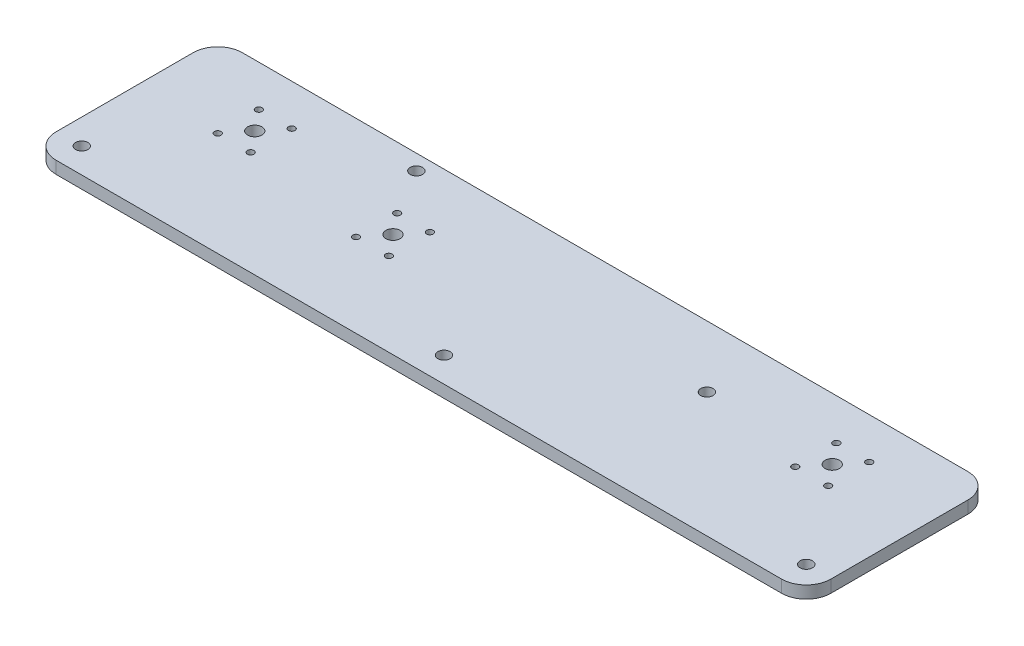
SolidWorks part; units mm, degrees
material "Policarbonato"
ref_plane "Plano frontal" through (0, 0, 0) normal (0, 0, 1) x (1, 0, 0)
ref_plane "Plano superior" through (0, 0, 0) normal (0, 1, 0) x (1, 0, 0)
ref_plane "Plano direito" through (0, 0, 0) normal (1, 0, 0) x (0, 0, -1)
sketch "Esboço1" plane through (0, 0, 0) normal (0, 1, 0) x (1, 0, 0)
  line L4 (132.965, 0) -> (148.965, 0) construction
  line L6 (188.965, -38.6487) -> (188.965, 28)
  line L7 (176.965, 40) -> (-176.0908, 40)
  line L8 (-188.0908, 28) -> (-188.0908, -38.6487)
  line L9 (132.965, 0) -> (132.965, 20) construction
  line L11 (132.965, 20) -> (148.965, 20) construction
  line L12 (148.965, 0) -> (148.965, 20) construction
  line L13 (132.965, 0) -> (148.965, 20) construction
  line L14 (132.965, 20) -> (148.965, 0) construction
  line L15 (-148.0908, 0) -> (-132.0908, 0) construction
  line L16 (-148.0908, 0) -> (-148.0908, 20) construction
  line L17 (-148.0908, 20) -> (-132.0908, 20) construction
  line L18 (-132.0908, 0) -> (-132.0908, 20) construction
  line L19 (-176.0908, -50.6487) -> (176.965, -50.6487)
  line L20 (-148.0908, 0) -> (-132.0908, 20) construction
  line L21 (-148.0908, 20) -> (-132.0908, 0) construction
  line L22 (-70.8033, -10) -> (-54.8033, -10) construction
  line L23 (-70.8033, -10) -> (-70.8033, 10) construction
  line L24 (-70.8033, 10) -> (-54.8033, 10) construction
  line L25 (-54.8033, -10) -> (-54.8033, 10) construction
  line L26 (-70.8033, -10) -> (-54.8033, 10) construction
  line L27 (-70.8033, 10) -> (-54.8033, -10) construction
  arc A0 (176.965, -50.6487) -> (188.965, -38.6487) centre (176.965, -38.6487) ccw
  arc A1 (188.965, 28) -> (176.965, 40) centre (176.965, 28) ccw
  arc A2 (-188.0908, 28) -> (-176.0908, 40) centre (-176.0908, 28) cw
  arc A3 (-188.0908, -38.6487) -> (-176.0908, -50.6487) centre (-176.0908, -38.6487) ccw
  circle A7 centre (-62.8033, 0) radius 3.5
  circle A8 centre (176.7481, -38.4318) radius 3
  circle A9 centre (0.4371, -38.4318) radius 3
  circle A10 centre (79.965, 10) radius 3
  circle A11 centre (-140.0908, 10) radius 3.5
  circle A13 centre (-148.0908, 0) radius 1.6
  circle A14 centre (-132.0908, 0) radius 1.6
  circle A15 centre (-132.0908, 20) radius 1.6
  circle A16 centre (-148.0908, 20) radius 1.6
  circle A17 centre (-70.8033, -10) radius 1.6
  circle A18 centre (-70.8033, 10) radius 1.6
  circle A19 centre (-54.8033, 10) radius 1.6
  circle A20 centre (-54.8033, -10) radius 1.6
  circle A21 centre (-62.8033, 0) radius 25 construction
  circle A22 centre (-83.9303, 32.5) radius 7.5 construction
  circle A23 centre (-140.0908, 10) radius 48 construction
  circle A24 centre (-83.9303, 32.5) radius 3
  circle A25 centre (-175.8739, -38.4318) radius 3
  circle A26 centre (140.965, 10) radius 3.5
  circle A27 centre (148.965, 0) radius 1.6
  circle A28 centre (148.965, 20) radius 1.6
  circle A29 centre (132.965, 0) radius 1.6
  circle A30 centre (132.965, 20) radius 1.6
  point P33 (0.4371, 40)
  dimension "D2" = 377.0558
  dimension "D4" = 7
  dimension "D6" = 12.2169
  dimension "D8" = 77.2875
  dimension "D10" = 48
  dimension "D12" = 16
  dimension "D15" = 20
  dimension "D17" = 6
  dimension "D1" = 12
  dimension "D7" = 40
  dimension "D9" = 30
  dimension "D11" = 7
  dimension "D16" = 3.2
  dimension "D20" = 3.2
  dimension "D25" = 56.1605
  dimension "D26" = 61
  dimension "D27" = 50
  dimension "D28" = 15
  dimension "D29" = 96
  dimension "D3" = 90.6487
  dimension "D5" = 12.2169
  dimension "D13" = 16
  dimension "D14" = 20
  dimension "D18" = 12.2169
  dimension "D19" = 30
  dimension "D21" = 16
  dimension "D22" = 20
  dimension "D23" = 48
  dimension "D24" = 7.5
extrude "Ressalto-extrusão1" add sketch "Esboço1" against normal blind 6
